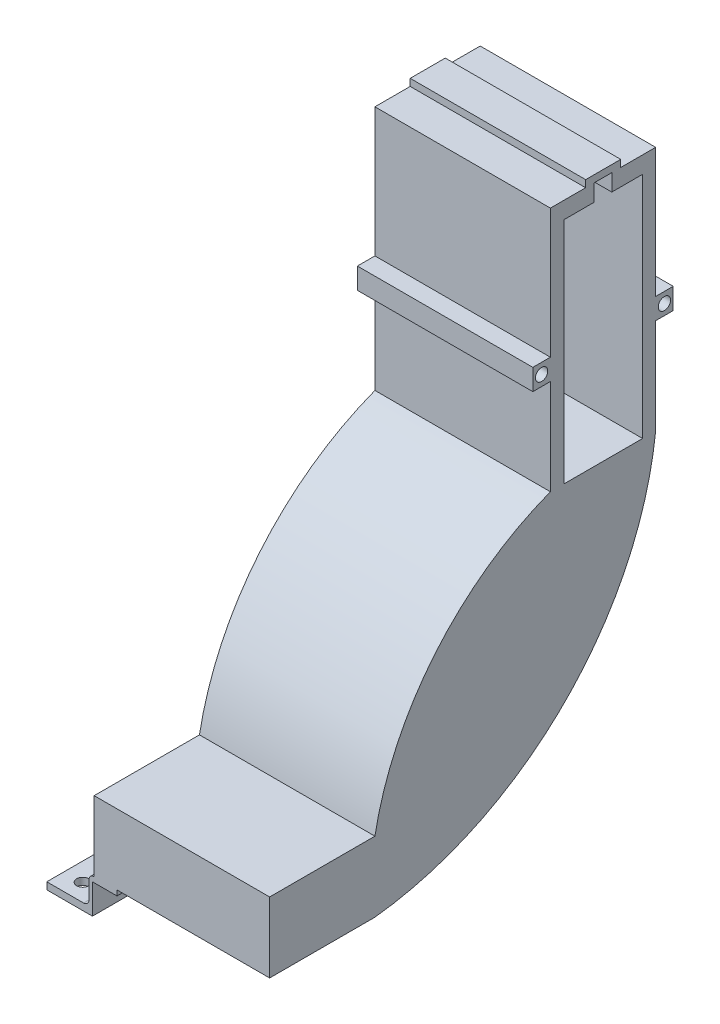
SolidWorks part; units mm, degrees
ref_plane "Front Plane" through (0, 0, 0) normal (0, 0, 1) x (1, 0, 0)
ref_plane "Top Plane" through (0, 0, 0) normal (0, 1, 0) x (1, 0, 0)
ref_plane "Right Plane" through (0, 0, 0) normal (1, 0, 0) x (0, 0, -1)
sketch "Sketch1" plane through (0, 0, 0) normal (0, 1, 0) x (1, 0, 0)
  line L1 (0, 0) -> (20, 0)
  line L2 (0, 0) -> (0, 30)
  line L3 (0, 30) -> (20, 30)
  line L4 (20, 0) -> (20, 30)
  dimension "D1" = 30
  dimension "D2" = 20
extrude "Boss-Extrude1" add sketch "Sketch1" along normal blind 10
sketch "Sketch2" plane through (0, 0, 0) normal (0, 0, 1) x (1, 0, 0)
  line L0 (0, 0) -> (20, 0) construction
  line L1 (0, 10) -> (12, 10)
  line L2 (0, 10) -> (0, 2)
  line L3 (0, 2) -> (12, 2)
  line L4 (12, 10) -> (12, 2)
  line L5 (20, 10) -> (20, 0) construction
  dimension "D1" = 2
  dimension "D2" = 8
extrude "Cut-Extrude1" cut sketch "Sketch2" against normal through all
fillet "Fillet1" radius 1.5 1 edges at (12, 2, -15)
fillet "Fillet2" radius 1.5 1 edges at (12, 10, -15)
sketch "Sketch3" plane through (0, 0, 0) normal (0, 0, 1) x (1, 0, 0)
  line L0 (12, 3.5) -> (12, 8.5) construction
  line L1 (20, 0) -> (13, 0)
  line L2 (20, 0) -> (20, 8.5)
  line L3 (20, 8.5) -> (13, 8.5)
  line L4 (13, 0) -> (13, 8.5)
  line L5 (13.5, 10) -> (20, 10) construction
  dimension "D1" = 1
  dimension "D2" = 1.5
extrude "Cut-Extrude2" cut sketch "Sketch3" against normal through all
sketch "Sketch4" plane through (0, 2, 0) normal (0, 1, 0) x (1, 0, 0)
  line L3 (0, 30) -> (10.5, 30) construction
  circle A0 centre (5.25, 25) radius 1.75
  circle A1 centre (5.25, 5) radius 1.75
  point P4 (0, 0)
  point P5 (0, 0)
  point P8 (0, 0)
  point P9 (5.25, 30)
  point P10 (0, 0)
  point P11 (0, 0)
  point P12 (0, 0)
  point P13 (5.25, 5)
  dimension "D1" = 3.5
  dimension "D2" = 20
  dimension "D3" = 5
extrude "Cut-Extrude3" cut sketch "Sketch4" against normal through all
ref_plane "Plane7" through (13.5, 0, 0) normal (1, 0, 0) x (0, 0, -1)
sketch "Sketch12" plane through (13.5, 0, 0) normal (1, 0, 0) x (0, 0, -1)
  line L1 (0, 10) -> (30, 10)
  line L2 (0, 10) -> (0, 30)
  line L3 (0, 30) -> (30, 30)
  line L5 (80, 90) -> (80, 160)
  line L6 (80, 160) -> (90.05, 160)
  line L7 (110, 160) -> (110, 123.2)
  line L9 (106.28, 90) -> (83.82, 90)
  line L10 (106.28, 90) -> (106.28, 155.2)
  line L11 (106.28, 155.2) -> (97.5, 155.2)
  line L12 (83.82, 90) -> (83.82, 155.2)
  line L13 (110, 117.2) -> (110, 90)
  line L14 (115, 117.2) -> (110, 117.2)
  line L15 (115, 117.2) -> (115, 123.2)
  line L16 (115, 123.2) -> (110, 123.2)
  line L17 (95.05, 759.1109) -> (95.05, 90) construction
  line L18 (80, 117.2) -> (75, 117.2)
  line L19 (75, 117.2) -> (75, 123.2)
  line L20 (75, 123.2) -> (80, 123.2)
  line L21 (97.5, 160) -> (97.5, 155.2)
  line L23 (92.5, 155.2) -> (92.5, 160)
  line L24 (92.5, 160) -> (97.5, 160)
  line L25 (92.5, 155.2) -> (83.82, 155.2)
  line L26 (100.05, 160) -> (110, 160)
  line L27 (92.5, 160) -> (97.5, 160)
  line L28 (90.05, 160) -> (90.05, 162)
  line L29 (90.05, 162) -> (100.05, 162)
  line L30 (100.05, 160) -> (100.05, 162)
  line L31 (92.5, 160) -> (97.5, 160)
  arc A1 (30, 30) -> (80, 90) centre (108.6381, 15.3016) cw
  arc A2 (30, 10) -> (110, 90) centre (20, 100) ccw
  circle A3 centre (112.5, 120.2) radius 1.75
  circle A4 centre (77.5, 120.2) radius 1.75
  point P19 (80, 125)
  point P24 (112.5, 123.2)
  point P26 (115, 120.2)
  point P36 (95.05, 162)
  point P38 (100, 162.5013)
  point P43 (100.7904, 162)
  point P44 (99.5721, 162)
  dimension "D5" = 80
  dimension "D13" = 3.5
  dimension "D18" = 5
  dimension "D1" = 20
  dimension "D2" = 110
  dimension "D3" = 70
  dimension "D4" = 30
  dimension "D6" = 70
  dimension "D7" = 60
  dimension "D8" = 22.46
  dimension "D9" = 3.72
  dimension "D11" = 5
  dimension "D12" = 6
  dimension "D14" = 3
  dimension "D15" = 35
  dimension "D16" = 5
  dimension "D17" = 12.5
  dimension "D19" = 6
  dimension "D20" = 2.5
  dimension "D21" = 10
  dimension "D22" = 2
extrude "Boss-Extrude10" add sketch "Sketch12" along normal blind 10 separate body contours L25 L12 L9 L10 L11 L21 L24 L23
extrude "Boss-Extrude11" add sketch "Sketch12<11>" along normal blind 50 contours L1 A2 L13 L14 L15 L16 L7 L26 L30 L29 L31 L21 L11 L10 L9 L12 L25 L23 L24 L28 L6 L5 A1 L3 L2 A3 region at (13.5, 58.9625, -64.9941)
sketch "Sketch12<11>" plane through (13.5, 0, 0) normal (1, 0, 0) x (0, 0, -1) same geometry as "Sketch12"
extrude "Boss-Extrude12" add sketch "Sketch12<12>" along normal blind 50 contours L20 L19 L18 L5 A4 region at (13.5, 117.2781, -77.5)
sketch "Sketch12<12>" plane through (13.5, 0, 0) normal (1, 0, 0) x (0, 0, -1) same geometry as "Sketch12"
